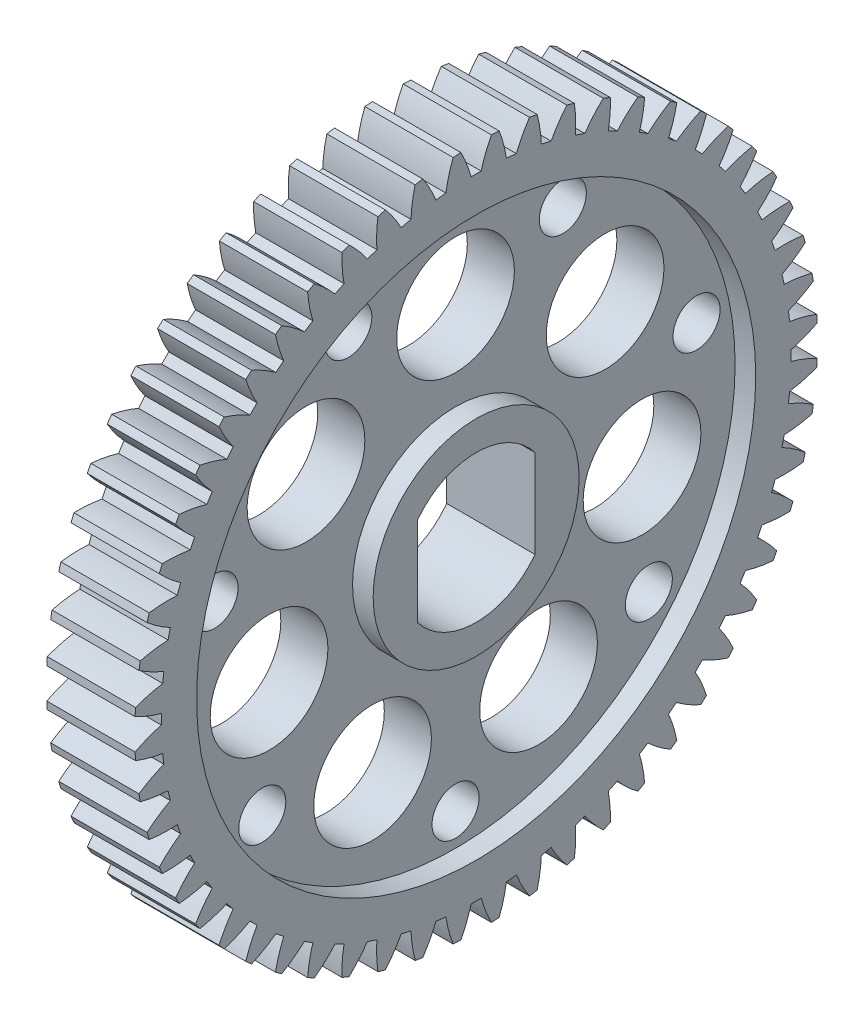
SolidWorks part; units mm, degrees
ref_plane "Plane1" through (0, 0, 0) normal (0, 0, 1) x (1, 0, 0)
ref_plane "Plane2" through (0, 0, 0) normal (0, 1, 0) x (1, 0, 0)
ref_plane "Plane3" through (0, 0, 0) normal (1, 0, 0) x (0, 0, -1)
other "Configuration Table"
sketch "HoldingSke" plane through (0, 0, 0) normal (0, 1, 0) x (1, 0, 0)
  line L0 (0, 0) -> (0.2796, -0.4145)
  line L1 (-15, 0) -> (100, 0) construction
  line L2 (0, 0) -> (-2.1039, 2.3779)
  line L3 (0, 0) -> (-11.863, 4.5341)
  line L4 (0, 0) -> (4.8292, 7.1596)
  line L5 (0, 0) -> (-46.8476, -17.4728)
  line L6 (0, 0) -> (-12.4344, -8.3896)
  line L7 (-2.1039, 2.3779) -> (8.6586, 51.2059)
  line L8 (-76.2, 54.61) -> (-76.1, 54.61)
  line L9 (-71.009, 38.7566) -> (-53.1078, 45.2721)
  line L10 (-76.2, 71.12) -> (104.1128, 71.12)
  line L11 (0, 0) -> (-15, 0)
  line L12 (-76.2, 101.6) -> (-76.133, 101.6)
  line L13 (24.9733, 27.94) -> (52.9518, 28.4284)
  line L14 (24.9733, 27.94) -> (24.9743, 27.94)
  line L15 (24.9733, 27.94) -> (100.4006, 29.5858)
  line L16 (-63.627, -2) -> (-12.827, -2)
  circle A0 centre (0, 0) radius 0.4
  circle A1 centre (0, 0) radius 37.5
  circle A2 centre (0, 0) radius 37.5
  circle A3 centre (0, 0) radius 0.4
  dimension "Num_teeth" = 56
  dimension "Pitch_radius" = 180.3128
  dimension "Width" = 15
  dimension "Thickness" = 15
sketch "BasProSke" plane through (0, 0, 0) normal (0, 1, 0) x (1, 0, 0)
  line L0 (-10, 0) -> (60, 0) construction
  line L1 (0, 0) -> (0, 58)
  line L2 (0, 0) -> (15, 0)
  line L3 (15, 0) -> (15, 58)
  line L4 (15, 58) -> (0, 58)
  dimension "Thickness" = 15
  dimension "Diameter" = 116
revolve "Base-Revolve" add sketch "BasProSke" angle 360 about L0
sketch "TooCutSke" plane through (0, 0, 0) normal (1, 0, 0) x (0, 0, -1)
  line L1 (0, 0) -> (0, 107) construction
  line L2 (0, 0) -> (-1.6878, 55.9746) construction
  line L3 (0, 0) -> (-6.2778, 111.7861) construction
  line L4 (-1.6878, 55.9746) -> (-3.1389, 55.8931) construction
  arc A0 (0.8509, 53.4922) -> (-0.8509, 53.4922) centre (0, 0) ccw
  arc A1 (2.608, 57.9668) -> (-2.608, 57.9668) centre (0, 0) ccw
  circle A2 centre (0, 0) radius 56 construction
  circle A3 centre (0, 0) radius 52.6228 construction
  arc A4 (-0.8509, 53.4922) -> (-2.608, 57.9668) centre (-22.4592, 47.5893) ccw
  arc A5 (2.608, 57.9668) -> (0.8509, 53.4922) centre (22.4592, 47.5893) ccw
extrude "ToothCut" cut sketch "TooCutSke" along normal through all
fillet "Breaks" [suppressed] radius 0.04 tangent propagation no
fillet "RootFillets" [suppressed] radius 0.501
pattern_circular "TeethCuts" count 56 every 6.429 about axis through (-10, 0, 0) along (1, 0, 0) of "ToothCut", "RootFillets", "Breaks"
sketch "HubNeaOneSke" plane through (0, 0, 0) normal (-1, 0, 0) x (0, 0, 1)
  circle A0 centre (0, 0) radius 37.5
  dimension "Diameter" = 75
extrude "HubNearOne" [suppressed] add sketch "HubNeaOneSke" along normal blind 35.0001
sketch "HubNeaBotSke" plane through (0, 0, 0) normal (-1, 0, 0) x (0, 0, 1)
  circle A0 centre (0, 0) radius 37.5
  dimension "Diameter" = 75
extrude "HubNearBoth" [suppressed] add sketch "HubNeaBotSke" along normal blind 17.5
ref_plane "FarPln" through (15, 0, 0) normal (1, 0, 0) x (0, 0, -1)
sketch "HubFarSke" plane through (15, 0, 0) normal (1, 0, 0) x (0, 0, -1)
  circle A0 centre (0, 0) radius 37.5
  dimension "Diameter" = 75
extrude "HubFar" [suppressed] add sketch "HubFarSke" along normal blind 17.5
sketch "BorSke" plane through (0, 0, 0) normal (1, 0, 0) x (0, 0, -1)
  circle A0 centre (0, 0) radius 0.4
  dimension "Diameter" = 0.8
extrude "Bore" cut sketch "BorSke" along normal mid plane 100.0001
sketch "KeySke" plane through (0, 0, 0) normal (1, 0, 0) x (0, 0, -1)
  line L0 (-0.05, 0) -> (-0.05, 0.5)
  line L1 (-0.05, 0.5) -> (0.05, 0.5)
  line L2 (0.05, 0.5) -> (0.05, 0)
  line L3 (0, 0) -> (0, 34) construction
  line L4 (-0.05, 0) -> (0.05, 0)
extrude "Keyway" [suppressed] cut sketch "KeySke" along normal mid plane 100.0001
pattern_circular "Keyway2" [suppressed] count 2 every 90 about axis through (-10, 0, 0) along (1, 0, 0)
sketch "Sketch1" plane through (15, 0, 0) normal (1, 0, 0) x (0, 0, -1)
  circle A0 centre (0, 0) radius 47.5
  dimension "D1" = 95
extrude "Cut-Extrude1" cut sketch "Sketch1" against normal blind 3.5
extrude "Cut-Extrude2" cut sketch "Sketch1<2>" along normal blind 3.5 from surface starting at face at (0, 0, -0.4)
sketch "Sketch1<2>" plane through (15, 0, 0) normal (1, 0, 0) x (0, 0, -1) same geometry as "Sketch1"
sketch "Sketch3" plane through (11.5, 0, 0) normal (1, 0, 0) x (0, 0, -1)
  circle A0 centre (0, 0) radius 17.5
  dimension "D1" = 35
extrude "Boss-Extrude1" add sketch "Sketch3" along normal blind 3.5 and the other way blind 11.5
sketch "Sketch4" plane through (15, 0, 0) normal (1, 0, 0) x (0, 0, -1)
  line L0 (0, 0) -> (0, 4.2947) construction
  line L1 (-10, 7.5) -> (-10, -7.5)
  line L2 (10, 7.5) -> (10, -7.5)
  arc A0 (10, 7.5) -> (-10, 7.5) centre (0, 0) ccw
  arc A1 (-10, -7.5) -> (10, -7.5) centre (0, 0) ccw
  dimension "D1" = 25
  dimension "D2" = 20
extrude "Cut-Extrude3" cut sketch "Sketch4" against normal through all
sketch "Sketch5" plane through (11.5, 0, 0) normal (1, 0, 0) x (0, 0, -1)
  line L0 (0, 0) -> (0, 27.1145) construction
  circle A0 centre (0, 0) radius 32.5 construction
  circle A1 centre (0, 32.5) radius 10
  dimension "D1" = 65
  dimension "D2" = 20
extrude "Cut-Extrude4" cut sketch "Sketch5" against normal through all
pattern_circular "CirPattern1" count 7 over 360 about axis through (0, 0, 0) along (1, 0, 0) of "Cut-Extrude4"
sketch "Sketch6" plane through (11.5, 0, 0) normal (1, 0, 0) x (0, 0, -1)
  line L0 (4.3388, 41.5097) -> (29.7484, 29.2731) construction
  line L1 (0, 0) -> (17.0436, 35.3914) construction
  line L2 (17.0436, 35.3914) -> (18.2231, 37.8407) construction
  circle A0 centre (0, 0) radius 42 construction
  circle A1 centre (0, 32.5) radius 10 construction
  circle A2 centre (25.4095, 20.2634) radius 10 construction
  circle A3 centre (18.2231, 37.8407) radius 4
  dimension "D1" = 84
  dimension "D2" = 8
extrude "Cut-Extrude5" cut sketch "Sketch6" against normal through all
pattern_circular "CirPattern2" count 7 over 360 about axis through (0, 0, 0) along (1, 0, 0) of "Cut-Extrude5" reverse direction yes
equation "' \"Module@HoldingSke\" = 6.35"
equation "' \"Num_teeth@HoldingSke\" = 12"
equation "' \"Ap@HoldingSke\" =  20"
equation "' \"Ap@HoldingSke\" = 20"
equation "' \"Width@HoldingSke\" = 0.5 * 25.4"
equation "' \"Hub_dia@HoldingSke\"= 1 * 25.4"
equation "' \"Hub_dia@HoldingSke\" = 1 * 25.4"
equation "' \"Overall_len@HoldingSke\" = 1.0 * 25.4"
equation "' \"Bore@HoldingSke\" = 0.75 * 25.4"
equation "' \"T_dim@HoldingSke\" = 0.1 * 25.4"
equation "' \"Width@KeySke\" = 0.25 * 25.4"
equation "' \"Show_teeth@HoldingSke\" = 13"
equation "' \"Backlash@HoldingSke\" = 0.009 * 25.4"
equation "' \"Addendum_fac@HoldingSke\" = 1.0"
equation "' \"Dedendum_fac@HoldingSke\" = 1.25"
equation "' \"Dedendum_add@HoldingSke\" = 0.00005 * 25.4"
equation "' \"Clearance_fac@HoldingSke\" = 0.25"
equation "\"Pitch@HoldingSke\" = 1 / \"Module@HoldingSke\""
equation "\"Overcut_dia@TooCutSke\" = (\"Num_teeth@HoldingSke\" + 2 * \"Addendum_fac@HoldingSke\") / \"Pitch@HoldingSke\" + 0.002 * 25.4"
equation "\"Pitch_dia@TooCutSke\" = \"Num_teeth@HoldingSke\" / \"Pitch@HoldingSke\""
equation "\"Base_dia@TooCutSke\" = \"Num_teeth@HoldingSke\" / \"Pitch@HoldingSke\" * cos((\"Ap@HoldingSke\"  * 3.14159265 / 180))"
equation "\"Root_dia@TooCutSke\" = (\"Num_teeth@HoldingSke\" + 2) / \"Pitch@HoldingSke\" - 2 * (\"Addendum_fac@HoldingSke\" + \"Dedendum_fac@HoldingSke\") / \"Pitch@HoldingSke\" - \"Dedendum_add@HoldingSke\" * 2"
equation "\"Half_ang@TooCutSke\" = 180 / \"Num_teeth@HoldingSke\""
equation "\"Half_CT@TooCutSke\" = \"Num_teeth@HoldingSke\" / \"Pitch@HoldingSke\" * sin((3.14159265 / 2 / \"Num_teeth@HoldingSke\")) / 2 - 7 * \"Backlash@HoldingSke\" / 4"
equation "\"Flank_rad@TooCutSke\" = \"Num_teeth@HoldingSke\" / \"Pitch@HoldingSke\" / 5"
equation "\"Radius@RootFillets\" = \"Clearance_fac@HoldingSke\" / \"Pitch@HoldingSke\" + \"Dedendum_add@HoldingSke\""
equation "\"Break_rad@Breaks\" = 0.02 / \"Pitch@HoldingSke\""
equation "\"Thickness@HoldingSke\" = \"Width@HoldingSke\""
equation "\"OAL@HoldingSke\" = \"Thickness@HoldingSke\""
equation "\"MHD@HoldingSke\" = (\"Num_teeth@HoldingSke\" + 2) / \"Pitch@HoldingSke\" - 2 * (\"Addendum_fac@HoldingSke\" + \"Dedendum_fac@HoldingSke\")  / \"Pitch@HoldingSke\" - \"Dedendum_add@HoldingSke\" * 2"
equation "\"MBD@HoldingSke\" = (\"Num_teeth@HoldingSke\" + 2) / \"Pitch@HoldingSke\" - 2 * (\"Addendum_fac@HoldingSke\" + \"Dedendum_fac@HoldingSke\")  / \"Pitch@HoldingSke\" - \"Dedendum_add@HoldingSke\" * 2 - 0.002 * 25.4"
equation "\"MHD@HoldingSke\" = ((sgn( \"MHD@HoldingSke\" - \"Hub_dia@HoldingSke\" )-1)*( \"MHD@HoldingSke\" - \"Hub_dia@HoldingSke\" ))/-2+ \"Hub_dia@HoldingSke\""
equation "\"MBD@HoldingSke\" = ((sgn( \"MBD@HoldingSke\" - \"Bore@HoldingSke\" )-1)*( \"MBD@HoldingSke\" - \"Bore@HoldingSke\" ))/-2+ \"Bore@HoldingSke\""
equation "\"OAL@HoldingSke\" = ((sgn( \"OAL@HoldingSke\" - \"Overall_len@HoldingSke\" )+1)*( \"OAL@HoldingSke\" - \"Overall_len@HoldingSke\" ))/2 + \"Overall_len@HoldingSke\" + 0.000002 * 25.4"
equation "\"Num_teeth@TeethCuts\" = int( \"Show_teeth@HoldingSke\" ) + 1"
equation "\"Num_teeth@TeethCuts\" = ((sgn( \"Num_teeth@TeethCuts\" - \"Num_teeth@HoldingSke\" )-1)*( \"Num_teeth@TeethCuts\" - \"Num_teeth@HoldingSke\" ))/-2+ \"Num_teeth@HoldingSke\""
equation "\"Num_teeth@TeethCuts\" = ((sgn( \"Num_teeth@TeethCuts\" - 2.0)+1)*( \"Num_teeth@TeethCuts\" - 2.0))/2 +2.0"
equation "\"Angle@TeethCuts\" = 360.0 / \"Num_teeth@HoldingSke\""
equation "\"Diameter@BasProSke\" = (\"Num_teeth@HoldingSke\" + 2 * \"Addendum_fac@HoldingSke\") / \"Pitch@HoldingSke\""
equation "\"Thickness@BasProSke\"  = \"Thickness@HoldingSke\""
equation "' \"Fillet_rad@BasProSke\" =  \"Thickness@HoldingSke\" * 0.05"
equation "' \"Fillet_rad@BasProSke\" = \"Thickness@HoldingSke\" * 0.05"
equation "\"MHD@HoldingSke\" = ((sgn( \"MHD@HoldingSke\" - \"Root_dia@TooCutSke\" )-1)*( \"MHD@HoldingSke\" - \"Root_dia@TooCutSke\" ))/-2+ \"Root_dia@TooCutSke\""
equation "\"Diameter@HubNeaOneSke\" = \"MHD@HoldingSke\""
equation "\"Length@HubNearOne\" = \"OAL@HoldingSke\" - \"Thickness@BasProSke\""
equation "\"Diameter@HubNeaBotSke\" = \"MHD@HoldingSke\""
equation "\"Length@HubNearBoth\" = ( \"OAL@HoldingSke\" - \"Thickness@BasProSke\" ) / 2.0"
equation "\"Thickness@FarPln\" = \"Thickness@BasProSke\""
equation "\"Diameter@HubFarSke\" = \"MHD@HoldingSke\""
equation "\"Length@HubFar\" = ( \"OAL@HoldingSke\" - \"Thickness@BasProSke\" ) / 2.0"
equation "\"Diameter@BorSke\" = \"MBD@HoldingSke\""
equation "\"D1@Bore\" = \"OAL@HoldingSke\" * 2.0"
equation "\"D1@Keyway\" = \"OAL@HoldingSke\" * 2.0"
equation "\"Offset@KeySke\" = \"T_dim@HoldingSke\" + \"MBD@HoldingSke\" / 2.0"
